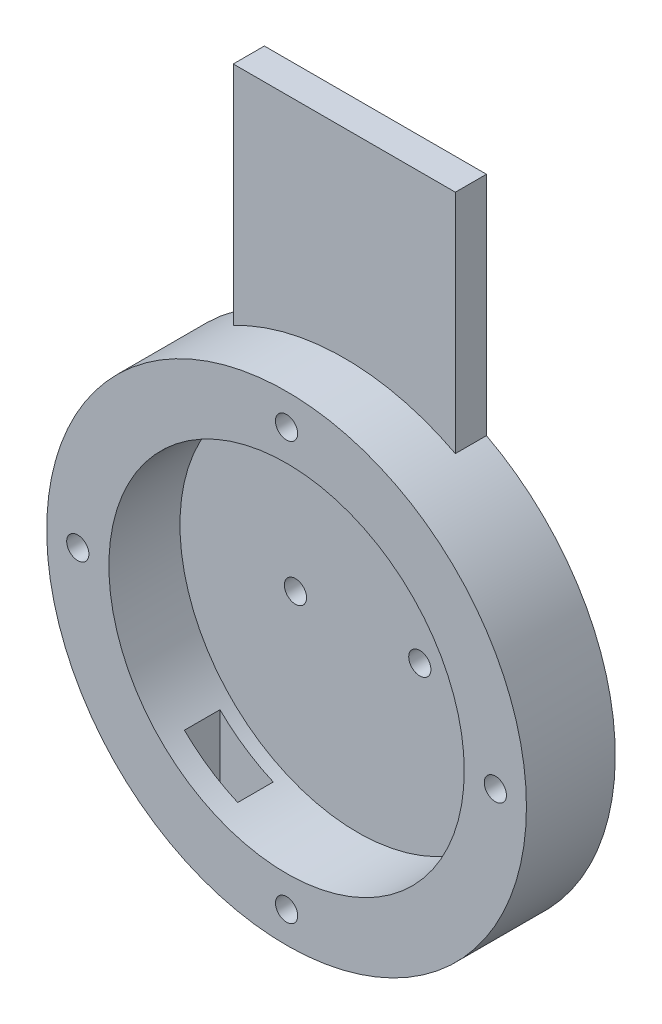
SolidWorks part; units mm, degrees
ref_plane "Front Plane" through (0, 0, 0) normal (0, 0, 1) x (1, 0, 0)
ref_plane "Top Plane" through (0, 0, 0) normal (0, 1, 0) x (1, 0, 0)
ref_plane "Right Plane" through (0, 0, 0) normal (1, 0, 0) x (0, 0, -1)
sketch "Sketch1" plane through (0, 0, 0) normal (0, 0, 1) x (1, 0, 0)
  circle A0 centre (0, 0) radius 27
  circle A1 centre (0, 0) radius 23.5 construction
  circle A2 centre (0, 23.5) radius 1.25
  circle A3 centre (23.5, 0) radius 1.25
  circle A4 centre (0, -23.5) radius 1.25
  circle A5 centre (-23.5, 0) radius 1.25
  circle A6 centre (0, 0) radius 20
  point P15 (0, 0)
  dimension "D1" = 54
  dimension "D2" = 47
  dimension "D3" = 2.5
  dimension "D5" = 40
  dimension "D4" = 4
extrude "Boss-Extrude1" add sketch "Sketch1" along normal blind 10
sketch "Sketch3" plane through (0, 0, 0) normal (0, 0, 1) x (1, 0, 0)
  circle A0 centre (0, 0) radius 20
  circle A1 centre (0, 0) radius 7 construction
  circle A2 centre (-7, 0) radius 1.25
  circle A3 centre (7, 0) radius 1.25
  circle A4 centre (0, 0) radius 11.5 construction
  dimension "D1" = 40
  dimension "D2" = 14
  dimension "D3" = 2.5
  dimension "D4" = 23
extrude "Boss-Extrude2" add sketch "Sketch3" along normal blind 2
sketch "Sketch5" plane through (0, 0, 0) normal (0, 0, 1) x (1, 0, 0)
  line L0 (0, -5.5) -> (0, 5.5) construction
  line L1 (-12.5, 23.9322) -> (-4.2519, 23.9322)
  line L2 (-12.5, 23.9322) -> (-12.5, 49.4145)
  line L3 (-12.5, 49.4145) -> (12.5, 49.4145)
  line L4 (12.5, 23.9322) -> (12.5, 49.4145)
  line L5 (4.2678, 23.9322) -> (0, 26.2545)
  line L6 (0, 26.2545) -> (-4.2519, 23.9322)
  line L7 (4.2678, 23.9322) -> (12.5, 23.9322)
  circle A0 centre (0, 0) radius 27 construction
  dimension "D1" = 12.5
  dimension "D2" = 25
extrude "Boss-Extrude3" add sketch "Sketch5" along normal blind 3.5
sketch "Sketch4" plane through (0, 0, 0) normal (0, 1, 0) x (1, 0, 0)
  line L0 (27, -10) -> (-27, -10) construction
  line L1 (-14, -3.5) -> (-8, -3.5)
  line L2 (-14, -3.5) -> (-14, -7.5)
  line L3 (-14, -7.5) -> (-8, -7.5)
  line L4 (-8, -3.5) -> (-8, -7.5)
  line L5 (0, -5.5) -> (0, 5.5) construction
  dimension "D1" = 4
  dimension "D2" = 6
  dimension "D3" = 2.5
  dimension "D4" = 8
extrude "Cut-Extrude1" cut sketch "Sketch4" against normal up to surface (25.7876 mm away) up to face at (27, 0, 10)
